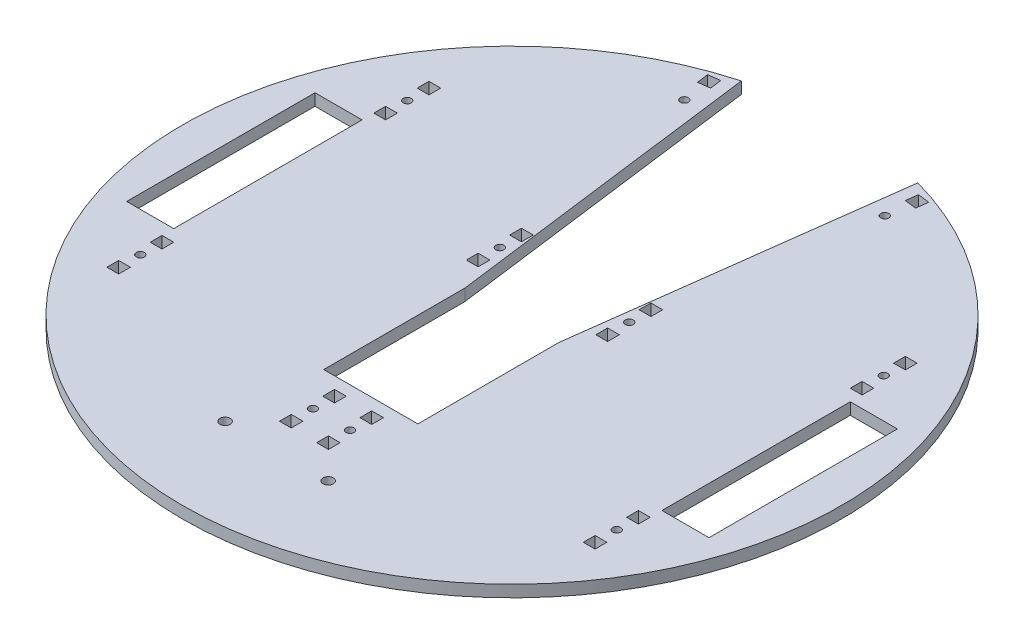
SolidWorks part; units mm, degrees
ref_plane "Front Plane" through (0, 0, 0) normal (0, 0, 1) x (1, 0, 0)
ref_plane "Top Plane" through (0, 0, 0) normal (0, 1, 0) x (1, 0, 0)
ref_plane "Right Plane" through (0, 0, 0) normal (1, 0, 0) x (0, 0, -1)
sketch "Bottom Plate" plane through (0, 0, 0) normal (0, 1, 0) x (1, 0, 0)
  line L0 (25.4, 0) -> (47.625, 171.3029)
  line L1 (-25.4, 0) -> (-47.625, 171.3029)
  line L2 (0, 0) -> (0, -177.8) construction
  line L3 (-25.4, 0) -> (-25.4, -76.2)
  line L4 (25.4, 0) -> (25.4, -76.2)
  line L5 (-25.4, 0) -> (25.4, 0) construction
  line L6 (-177.8, 0) -> (197.4825, 0) construction
  line L7 (125.3403, 72.009) -> (125.3403, -72.009) construction
  line L8 (131.6903, -50.8) -> (157.0903, -50.8)
  line L9 (131.6903, -50.8) -> (131.6903, 50.8)
  line L10 (131.6903, 50.8) -> (157.0903, 50.8)
  line L11 (157.0903, -50.8) -> (157.0903, 50.8)
  line L12 (131.6903, -50.8) -> (157.0903, 50.8) construction
  line L13 (131.6903, 50.8) -> (157.0903, -50.8) construction
  line L14 (-31.75, 36.83) -> (-31.75, 43.18)
  line L15 (31.75, 13.462) -> (38.1, 13.462)
  line L16 (38.1, 13.462) -> (38.1, 19.812)
  line L17 (38.1, 19.812) -> (31.75, 19.812)
  line L18 (31.75, 36.83) -> (38.1, 36.83)
  line L19 (38.1, 36.83) -> (38.1, 43.18)
  line L21 (131.6903, 50.8) -> (131.6903, 72.009) construction
  line L22 (131.6903, -50.8) -> (131.6903, -72.009) construction
  line L31 (-25.4, -76.2) -> (25.4, -76.2)
  line L32 (125.3403, 72.009) -> (131.6903, 72.009) construction
  line L33 (58.8162, 158.8529) -> (56.1364, 138.198) construction
  line L34 (52.5189, 159.6699) -> (58.8162, 158.8529)
  line L35 (52.5189, 159.6699) -> (53.3359, 165.9671)
  line L36 (53.3359, 165.9671) -> (59.6332, 165.1501)
  line L37 (56.4846, 165.5586) -> (52.9878, 138.6065) construction
  line L38 (58.8162, 158.8529) -> (59.6332, 165.1501)
  line L39 (52.5189, 159.6699) -> (59.6332, 165.1501) construction
  line L40 (53.3359, 165.9671) -> (58.8162, 158.8529) construction
  line L41 (56.1364, 138.198) -> (49.8392, 139.015) construction
  line L42 (49.8392, 139.015) -> (53.3359, 165.9671) construction
  line L43 (38.1, 43.18) -> (31.75, 43.18)
  line L44 (-31.75, 19.812) -> (-31.75, 13.462)
  line L45 (31.75, 19.812) -> (31.75, 13.462)
  line L46 (31.75, 36.83) -> (31.75, 43.18)
  line L47 (-38.1, 43.18) -> (-31.75, 43.18)
  line L48 (-38.1, 36.83) -> (-38.1, 43.18)
  line L49 (-31.75, 36.83) -> (-38.1, 36.83)
  line L50 (-38.1, 19.812) -> (-31.75, 19.812)
  line L51 (27.813, -127) -> (-27.813, -127) construction
  line L61 (10.033, -82.55) -> (10.033, -107.95) construction
  line L62 (-38.1, 13.462) -> (-38.1, 19.812)
  line L71 (-31.75, 13.462) -> (-38.1, 13.462)
  line L73 (125.3403, -72.009) -> (131.6903, -72.009) construction
  line L84 (-131.6903, 50.8) -> (-157.0903, -50.8) construction
  line L85 (-131.6903, -50.8) -> (-157.0903, 50.8) construction
  line L86 (-157.0903, -50.8) -> (-157.0903, 50.8)
  line L87 (-131.6903, -50.8) -> (-131.6903, 50.8)
  line L92 (-131.6903, -50.8) -> (-157.0903, -50.8)
  line L93 (-131.6903, 50.8) -> (-157.0903, 50.8)
  line L101 (-53.3359, 165.9671) -> (-58.8162, 158.8529) construction
  line L102 (-52.5189, 159.6699) -> (-59.6332, 165.1501) construction
  line L103 (-58.8162, 158.8529) -> (-59.6332, 165.1501)
  line L104 (-53.3359, 165.9671) -> (-59.6332, 165.1501)
  line L105 (-52.5189, 159.6699) -> (-53.3359, 165.9671)
  line L106 (-52.5189, 159.6699) -> (-58.8162, 158.8529)
  arc A0 (-47.625, 171.3029) -> (47.625, 171.3029) centre (0, 0) ccw
  circle A3 centre (54.0826, 147.0448) radius 2.159
  circle A4 centre (34.925, 28.321) radius 2.159
  circle A6 centre (27.813, -127) radius 2.794
  circle A7 centre (-27.813, -127) radius 2.794
  circle A9 centre (-34.925, 28.321) radius 2.159
  circle A12 centre (-54.0826, 147.0448) radius 2.159
  point P2 (56.0761, 162.41)
  point P13 (144.3903, 0)
  point P74 (0, -127)
  point P90 (34.925, 19.812)
  point P106 (-144.3903, 0)
  point P129 (-56.0761, 162.41)
  line B0 (128.5153, 57.15) -> (128.5153, 86.868) construction
  line B1 (126.3563, 72.009) -> (130.6743, 72.009) construction
  line B2 (125.3403, 80.518) -> (131.6903, 80.518)
  line B3 (125.3403, 80.518) -> (125.3403, 86.868)
  line B4 (125.3403, 86.868) -> (131.6903, 86.868)
  line B5 (131.6903, 80.518) -> (131.6903, 86.868)
  line B6 (125.3403, 80.518) -> (131.6903, 86.868) construction
  line B7 (125.3403, 86.868) -> (131.6903, 80.518) construction
  line B8 (125.3403, 57.15) -> (131.6903, 63.5) construction
  line B9 (125.3403, 63.5) -> (131.6903, 57.15) construction
  line B10 (131.6903, 63.5) -> (131.6903, 57.15)
  line B11 (125.3403, 57.15) -> (131.6903, 57.15)
  line B12 (125.3403, 63.5) -> (125.3403, 57.15)
  line B13 (125.3403, 63.5) -> (131.6903, 63.5)
  circle B14 centre (128.5153, 72.009) radius 2.159
  line B15 (128.5153, -57.15) -> (128.5153, -86.868) construction
  line B16 (126.3563, -72.009) -> (130.6743, -72.009) construction
  line B17 (125.3403, -80.518) -> (131.6903, -80.518)
  line B18 (125.3403, -80.518) -> (125.3403, -86.868)
  line B19 (125.3403, -86.868) -> (131.6903, -86.868)
  line B20 (131.6903, -80.518) -> (131.6903, -86.868)
  line B21 (125.3403, -80.518) -> (131.6903, -86.868) construction
  line B22 (125.3403, -86.868) -> (131.6903, -80.518) construction
  line B23 (125.3403, -57.15) -> (131.6903, -63.5) construction
  line B24 (125.3403, -63.5) -> (131.6903, -57.15) construction
  line B25 (131.6903, -63.5) -> (131.6903, -57.15)
  line B26 (125.3403, -57.15) -> (131.6903, -57.15)
  line B27 (125.3403, -63.5) -> (125.3403, -57.15)
  line B28 (125.3403, -63.5) -> (131.6903, -63.5)
  circle B29 centre (128.5153, -72.009) radius 2.159
  line B30 (-128.5153, 57.15) -> (-128.5153, 86.868) construction
  line B31 (-130.6743, 72.009) -> (-126.3563, 72.009) construction
  line B32 (-131.6903, 80.518) -> (-125.3403, 80.518)
  line B33 (-131.6903, 80.518) -> (-131.6903, 86.868)
  line B34 (-131.6903, 86.868) -> (-125.3403, 86.868)
  line B35 (-125.3403, 80.518) -> (-125.3403, 86.868)
  line B36 (-131.6903, 80.518) -> (-125.3403, 86.868) construction
  line B37 (-131.6903, 86.868) -> (-125.3403, 80.518) construction
  line B38 (-131.6903, 57.15) -> (-125.3403, 63.5) construction
  line B39 (-131.6903, 63.5) -> (-125.3403, 57.15) construction
  line B40 (-125.3403, 63.5) -> (-125.3403, 57.15)
  line B41 (-131.6903, 57.15) -> (-125.3403, 57.15)
  line B42 (-131.6903, 63.5) -> (-131.6903, 57.15)
  line B43 (-131.6903, 63.5) -> (-125.3403, 63.5)
  circle B44 centre (-128.5153, 72.009) radius 2.159
  line B45 (-128.5153, -57.15) -> (-128.5153, -86.868) construction
  line B46 (-130.6743, -72.009) -> (-126.3563, -72.009) construction
  line B47 (-131.6903, -80.518) -> (-125.3403, -80.518)
  line B48 (-131.6903, -80.518) -> (-131.6903, -86.868)
  line B49 (-131.6903, -86.868) -> (-125.3403, -86.868)
  line B50 (-125.3403, -80.518) -> (-125.3403, -86.868)
  line B51 (-131.6903, -80.518) -> (-125.3403, -86.868) construction
  line B52 (-131.6903, -86.868) -> (-125.3403, -80.518) construction
  line B53 (-131.6903, -57.15) -> (-125.3403, -63.5) construction
  line B54 (-131.6903, -63.5) -> (-125.3403, -57.15) construction
  line B55 (-125.3403, -63.5) -> (-125.3403, -57.15)
  line B56 (-131.6903, -57.15) -> (-125.3403, -57.15)
  line B57 (-131.6903, -63.5) -> (-131.6903, -57.15)
  line B58 (-131.6903, -63.5) -> (-125.3403, -63.5)
  circle B59 centre (-128.5153, -72.009) radius 2.159
  line B60 (10.033, -112.268) -> (10.033, -82.55) construction
  line B61 (7.874, -97.409) -> (12.192, -97.409) construction
  line B62 (6.858, -88.9) -> (13.208, -88.9)
  line B63 (6.858, -88.9) -> (6.858, -82.55)
  line B64 (6.858, -82.55) -> (13.208, -82.55)
  line B65 (13.208, -88.9) -> (13.208, -82.55)
  line B66 (6.858, -88.9) -> (13.208, -82.55) construction
  line B67 (6.858, -82.55) -> (13.208, -88.9) construction
  line B68 (6.858, -112.268) -> (13.208, -105.918) construction
  line B69 (6.858, -105.918) -> (13.208, -112.268) construction
  line B70 (13.208, -105.918) -> (13.208, -112.268)
  line B71 (6.858, -112.268) -> (13.208, -112.268)
  line B72 (6.858, -105.918) -> (6.858, -112.268)
  line B73 (6.858, -105.918) -> (13.208, -105.918)
  circle B74 centre (10.033, -97.409) radius 2.159
  line B75 (10.033, -112.268) -> (10.033, -82.55) construction
  line B76 (12.192, -97.409) -> (7.874, -97.409) construction
  line B77 (13.208, -88.9) -> (6.858, -88.9)
  line B78 (13.208, -88.9) -> (13.208, -82.55)
  line B79 (13.208, -82.55) -> (6.858, -82.55)
  line B80 (6.858, -88.9) -> (6.858, -82.55)
  line B81 (13.208, -88.9) -> (6.858, -82.55) construction
  line B82 (13.208, -82.55) -> (6.858, -88.9) construction
  line B83 (13.208, -112.268) -> (6.858, -105.918) construction
  line B84 (13.208, -105.918) -> (6.858, -112.268) construction
  line B85 (6.858, -105.918) -> (6.858, -112.268)
  line B86 (13.208, -112.268) -> (6.858, -112.268)
  line B87 (13.208, -105.918) -> (13.208, -112.268)
  line B88 (13.208, -105.918) -> (6.858, -105.918)
  circle B89 centre (10.033, -97.409) radius 2.159
  line B90 (10.033, -112.268) -> (10.033, -82.55) construction
  line B91 (7.874, -97.409) -> (12.192, -97.409) construction
  line B92 (6.858, -88.9) -> (13.208, -88.9)
  line B93 (6.858, -88.9) -> (6.858, -82.55)
  line B94 (6.858, -82.55) -> (13.208, -82.55)
  line B95 (13.208, -88.9) -> (13.208, -82.55)
  line B96 (6.858, -88.9) -> (13.208, -82.55) construction
  line B97 (6.858, -82.55) -> (13.208, -88.9) construction
  line B98 (6.858, -112.268) -> (13.208, -105.918) construction
  line B99 (6.858, -105.918) -> (13.208, -112.268) construction
  line B100 (13.208, -105.918) -> (13.208, -112.268)
  line B101 (6.858, -112.268) -> (13.208, -112.268)
  line B102 (6.858, -105.918) -> (6.858, -112.268)
  line B103 (6.858, -105.918) -> (13.208, -105.918)
  circle B104 centre (10.033, -97.409) radius 2.159
  line B105 (10.033, -112.268) -> (10.033, -82.55) construction
  line B106 (12.192, -97.409) -> (7.874, -97.409) construction
  line B107 (13.208, -88.9) -> (6.858, -88.9)
  line B108 (13.208, -88.9) -> (13.208, -82.55)
  line B109 (13.208, -82.55) -> (6.858, -82.55)
  line B110 (6.858, -88.9) -> (6.858, -82.55)
  line B111 (13.208, -88.9) -> (6.858, -82.55) construction
  line B112 (13.208, -82.55) -> (6.858, -88.9) construction
  line B113 (13.208, -112.268) -> (6.858, -105.918) construction
  line B114 (13.208, -105.918) -> (6.858, -112.268) construction
  line B115 (6.858, -105.918) -> (6.858, -112.268)
  line B116 (13.208, -112.268) -> (6.858, -112.268)
  line B117 (13.208, -105.918) -> (13.208, -112.268)
  line B118 (13.208, -105.918) -> (6.858, -105.918)
  circle B119 centre (10.033, -97.409) radius 2.159
  line B120 (-10.033, -112.268) -> (-10.033, -82.55) construction
  line B121 (-7.874, -97.409) -> (-12.192, -97.409) construction
  line B122 (-6.858, -88.9) -> (-13.208, -88.9)
  line B123 (-6.858, -88.9) -> (-6.858, -82.55)
  line B124 (-6.858, -82.55) -> (-13.208, -82.55)
  line B125 (-13.208, -88.9) -> (-13.208, -82.55)
  line B126 (-6.858, -88.9) -> (-13.208, -82.55) construction
  line B127 (-6.858, -82.55) -> (-13.208, -88.9) construction
  line B128 (-6.858, -112.268) -> (-13.208, -105.918) construction
  line B129 (-6.858, -105.918) -> (-13.208, -112.268) construction
  line B130 (-13.208, -105.918) -> (-13.208, -112.268)
  line B131 (-6.858, -112.268) -> (-13.208, -112.268)
  line B132 (-6.858, -105.918) -> (-6.858, -112.268)
  line B133 (-6.858, -105.918) -> (-13.208, -105.918)
  circle B134 centre (-10.033, -97.409) radius 2.159
  dimension "D1" = 355.6
  dimension "D11" = 6.35
  dimension "D12" = 6.35
  dimension "D14" = 6.35
  dimension "D20" = 4.318
  dimension "D21" = 6.35
  dimension "D24" = 6.35
  dimension "D28" = 6.35
  dimension "D15" = 5.588
  dimension "D36" = 5.588
  dimension "D27" = 6.35
  dimension "D23" = 4.318
  dimension "D39" = 6.35
  dimension "D4" = 101.6
  dimension "D5" = 25.4
  dimension "D6" = 12.7
  dimension "D7" = 89.662
  dimension "D8" = 6.35
  dimension "D9" = 6.35
  dimension "D10" = 6.35
  dimension "D13" = 6.858
  dimension "D16" = 6.35
  dimension "D18" = 6.35
  dimension "D19" = 6.35
  dimension "D22" = 10.16
  dimension "D25" = 6.35
  dimension "D26" = 95.25
  dimension "D37" = 55.626
  dimension "D38" = 50.8
  dimension "D41" = 50.8
  dimension "D42" = 76.2
sketch_block_instance "Female T-Slot Assembly-1"
sketch_block "Female T-Slot Assembly" parameters "D4"=4.318, "D1"=6.35, "D2"=6.35, "D3"=6.35
sketch_block_instance "Female T-Slot Assembly-3"
sketch_block_instance "Female T-Slot Assembly-1"
sketch_block_instance "Female T-Slot Assembly-10"
sketch_block_instance "Female T-Slot Assembly-12"
sketch_block_instance "Female T-Slot Assembly-14"
sketch_block_instance "Female T-Slot Assembly-15"
sketch_block_instance "Female T-Slot Assembly-16"
sketch_block_instance "Female T-Slot Assembly-17"
extrude "Boss-Extrude1" add sketch "Bottom Plate" against normal blind 6.35 contours L1 A0 L0 L4 L31 L3 B122 B125 B124 B123 B74 B59 B58 B57 B56 B55 B42 B43 B40 B41 B35 B32 B33 B34 B17 B20 B19 B18 B14 A12 A7 A6 A4 A3 L105 L106 region at (41.4543, 0, -85.0103)
equation "\"Ball Diameter\"= 1.75in"
equation "\"Sheet Thickness\"= 0.25in"
equation "\"D10@Bottom Plate\" = \"Sheet Thickness\""
equation "\"Screw Diameter\"= .17in"
equation "\"Robot Diameter\"= 14in"
equation "\"D1@Bottom Plate\"=\"Robot Diameter\""
equation "\"D16@Bottom Plate\"=\"Sheet Thickness\""
equation "\"D18@Bottom Plate\"=\"Sheet Thickness\""
equation "\"D20@Bottom Plate\"=\"Screw Diameter\""
equation "\"Castor Screw Diameter\"= 0.22in"
equation "\"D15@Bottom Plate\"=\"Castor Screw Diameter\""
equation "\"D36@Bottom Plate\"=\"Castor Screw Diameter\""
equation "\"Wheel Diameter\" = 4in"
equation "\"D4@Bottom Plate\"=\"Wheel Diameter\""
equation "\"Nut Diameter\" = 8.4mm"
equation "\"Nut Height\" = 2.9mm"
equation "\"Screw Height\" = 0.55in"
equation "\"Pulley Diameter\" = 1in"
equation "\"Reactor Height\" = 14in"
equation "\"Elevator Height\" = 11.5in"
equation "\"Elevator Width\" = \"Ball Diameter\" + 0.25in"
equation "\"Elevator Bearing Diameter\" = sqr(2*(\"Sheet Thickness\"^2)) + 0.2in"
equation "\"Elevator Axle Length\" = \"Elevator Width\" + 8*\"Sheet Thickness\""
equation "\"D41@Bottom Plate\"=\"Elevator Width\""
equation "\"D8@Bottom Plate\" = \"Sheet Thickness\""
equation "\"D23@Bottom Plate\"=\"Screw Diameter\""
equation "\"D24@Bottom Plate\"=\"Sheet Thickness\""
equation "\"D9@Bottom Plate\"=\"Sheet Thickness\""
equation "\"D25@Bottom Plate\"=\"Sheet Thickness\""
equation "\"D19@Bottom Plate\"=\"Sheet Thickness\""
equation "\"D27@Bottom Plate\"=\"Sheet Thickness\""
equation "\"D7@Bottom Plate\"=(\"Elevator Clearance from Axis\") + 1in - (\"Pulley Diameter\"/2 + \"Sheet Thickness\")"
equation "\"D28@Bottom Plate\"=\"Sheet Thickness\""
equation "\"D39@Bottom Plate\"=\"Sheet Thickness\""
equation "\"Elevator Axle Endcap Diameter\" = \"Pulley Diameter\" + 0.25in"
equation "\"Elevator Clearance from Axis\" = 3.28in"
equation "\"D12@Bottom Plate\"=\"Sheet Thickness\""
equation "\"D14@Bottom Plate\"=\"Sheet Thickness\""
